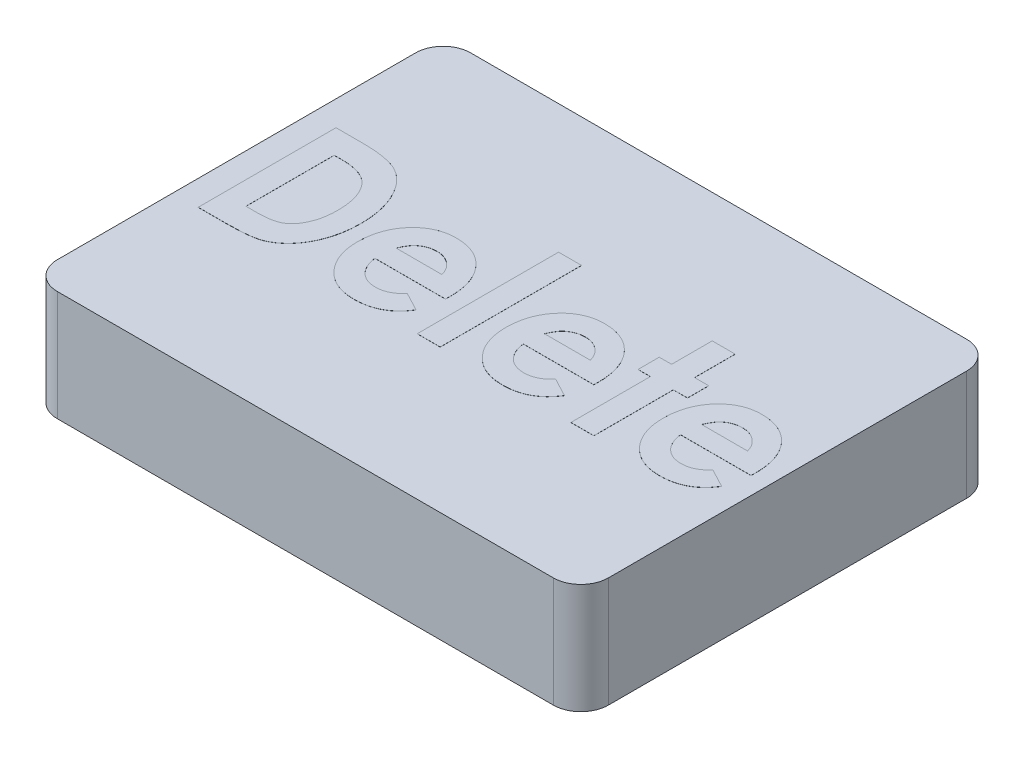
SolidWorks part; units mm, degrees
ref_plane "Front Plane" through (0, 0, 0) normal (0, 0, 1) x (1, 0, 0)
ref_plane "Top Plane" through (0, 0, 0) normal (0, 1, 0) x (1, 0, 0)
ref_plane "Right Plane" through (0, 0, 0) normal (1, 0, 0) x (0, 0, -1)
sketch "Sketch1" plane through (0, 0, 0) normal (0, 1, 0) x (1, 0, 0)
  line L0 (0, 0) -> (12.7, 0)
  line L1 (12.7, 0) -> (12.7, 9.525)
  line L2 (12.7, 9.525) -> (0, 9.525)
  line L3 (0, 9.525) -> (0, 0)
  dimension "D1" = 12.7
  dimension "D2" = 9.525
extrude "Boss-Extrude1" add sketch "Sketch1" along normal blind 2.54
fillet "Fillet1" radius 0.635 4 edges at (0, 1.27, -9.525) (12.7, 1.27, -9.525) (12.7, 1.27, 0) (0, 1.27, 0)
shell "Shell1" thickness 0.635 removed face at (6.35, 0, -4.7625)
sketch "Sketch2" plane through (0, 1.905, 0) normal (0, -1, 0) x (-1, 0, 0)
  line L0 (-0.635, 4.7625) -> (-12.065, 4.7625) construction
  line L1 (-0.635, 8.89) -> (-0.635, 0.635) construction
  line L2 (-12.065, 0.635) -> (-12.065, 8.89) construction
  line L3 (-6.35, 0.635) -> (-6.35, 8.89) construction
  line L4 (-0.635, 0.635) -> (-12.065, 0.635) construction
  line L5 (-12.065, 8.89) -> (-0.635, 8.89) construction
  circle A0 centre (-6.35, 4.7625) radius 2.54
  dimension "D1" = 5.08
extrude "Boss-Extrude2" add sketch "Sketch2" along normal up to surface (1.905 mm away) up to face at (6.35, 0, -4.7625)
sketch "Sketch3" plane through (0, 2.54, 0) normal (0, 1, 0) x (1, 0, 0)
  line L0 (0.635, 0) -> (12.065, 0) construction
  line L1 (0, 8.89) -> (0, 0.635) construction
  text T0 "<b>Delete</b>" font "Century Gothic" height 3.175
  dimension "D1" = 3.302
  dimension "D2" = 0.254
extrude "Boss-Extrude3" add sketch "Sketch3" along normal blind 0.0025
